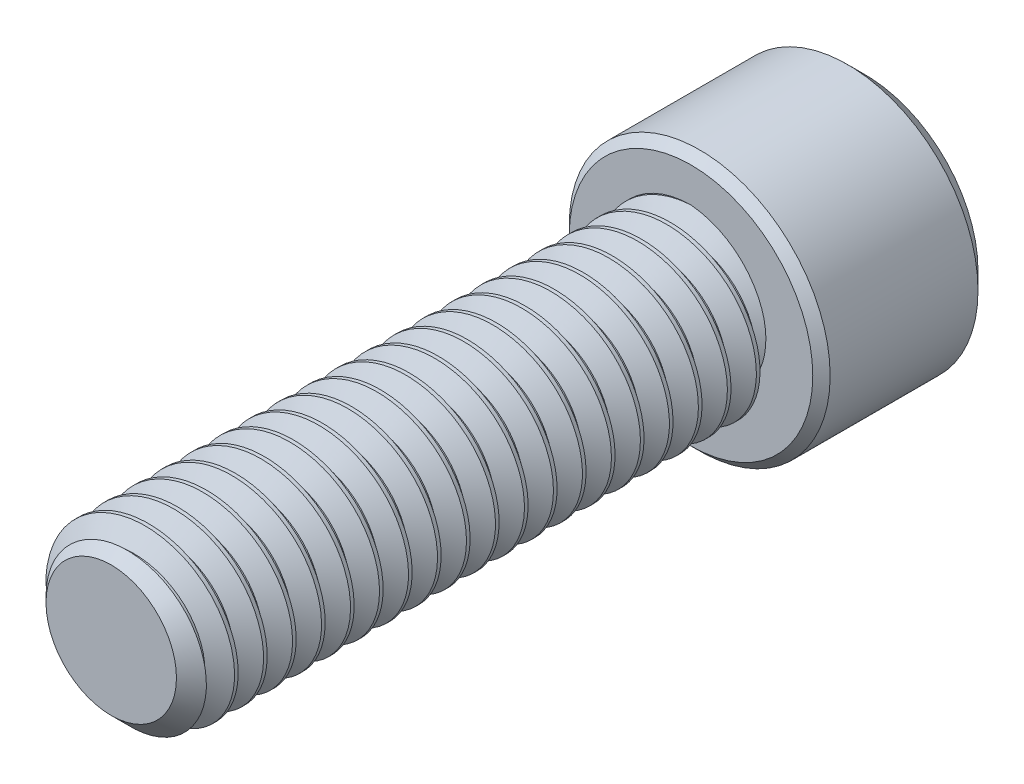
SolidWorks part; units mm, degrees
ref_plane "Front Plane" through (0, 0, 0) normal (0, 0, 1) x (1, 0, 0)
ref_plane "Top Plane" through (0, 0, 0) normal (0, 1, 0) x (1, 0, 0)
ref_plane "Right Plane" through (0, 0, 0) normal (1, 0, 0) x (0, 0, -1)
sketch "Sketch1" plane through (0, 0, 0) normal (0, 0, 1) x (1, 0, 0)
  line L0 (0, 4.7625) -> (0, -4.7625) construction
  circle A0 centre (0, 0) radius 4.7625
  dimension "OD" = 9.525
extrude "Extrude1" add sketch "Sketch1" against normal blind 31.75
sketch "Sketch2" plane through (0, 0, 0) normal (0, 0, 1) x (1, 0, 0)
  circle A0 centre (0, 0) radius 4.7625 construction
  circle A1 centre (0, 0) radius 4.7625
curve "Helix/Spiral1" pitch 1.5875 height 33.3375 turns 21 parameters "pitch"=1.5875
chamfer "Chamfer3" distance 1.1906 angle 45 1 edges at (4.7625, 0, 0)
sketch "Sketch3" plane through (0, 0, 0) normal (1, 0, 0) x (0, 0, -1)
  line L0 (-1.3891, 4.7625) -> (-0.7938, 3.7314)
  line L1 (-0.7938, 3.7314) -> (-0.5953, 3.7314)
  line L2 (-0.5953, 3.7314) -> (0, 4.7625)
  line L3 (-1.3891, 4.7625) -> (0, 4.7625)
  line L4 (-0.6945, 4.7625) -> (-0.6945, 3.7314) construction
  line L5 (-1.0914, 4.2469) -> (-0.2977, 4.2469) construction
  line L6 (0, 4.7625) -> (0, -4.7625) construction
  dimension "D1" = 0.1984
  dimension "D2" = 0.7937
  dimension "D3" = 60
sweep "Cut-Sweep1" cut profiles "Sketch3" path "Helix/Spiral1"
sketch "Sketch6" plane through (0, 0, -31.75) normal (0, 0, -1) x (-1, 0, 0)
  circle A0 centre (0, 0) radius 7.1438
  dimension "head dia" = 14.2875
extrude "Extrude2" add sketch "Sketch6" along normal blind 9.525
sketch "Sketch7" plane through (0, 0, -41.275) normal (0, 0, -1) x (-1, 0, 0)
  line L1 (0, 4.5827) -> (-3.9688, 2.2914)
  line L2 (-3.9688, 2.2914) -> (-3.9688, -2.2914)
  line L3 (-3.9688, -2.2914) -> (0, -4.5827)
  line L4 (0, -4.5827) -> (3.9688, -2.2914)
  line L5 (3.9688, -2.2914) -> (3.9687, 2.2914)
  line L6 (3.9687, 2.2914) -> (0, 4.5827)
  circle A0 centre (0, 0) radius 3.9688 construction
  dimension "hex dia" = 7.9375
extrude "Cut-Extrude1" cut sketch "Sketch7" against normal blind 5.9531
sketch "Sketch8" plane through (0, 0, -41.275) normal (0, 0, -1) x (-1, 0, 0)
  circle A0 centre (0, 0) radius 4.5827
extrude "Cut-Extrude2" cut sketch "Sketch8" against normal blind 0.9525 draft 45
chamfer "Chamfer1" distance 0.9525 angle 45 1 edges at (-7.1438, 0, -41.275)
chamfer "Chamfer2" distance 0.4763 angle 45 1 edges at (-7.1438, 0, -31.75)
sketch "Sketch9" plane through (0, 0, 0) normal (1, 0, 0) x (0, 0, -1)
  line L0 (0, 4.7625) -> (0, -4.7625) construction
  line L1 (8.7313, 4.7625) -> (8.7313, -4.7625) construction
  line L2 (31.75, 7.1437) -> (31.75, -7.1438) construction
  line L3 (41.275, 7.1437) -> (41.275, -7.1437) construction
  line L4 (41.275, 0) -> (0, 0) construction
  dimension "D1" = 8.7312
  dimension "D2" = 9.525
  dimension "D3" = 14.2875
  dimension "D4" = 0.635
  dimension "D5" = 0.3302
equation "\"D3@Helix/Spiral1\" = \"screw length@Extrude1\"+\"pitch@Helix/Spiral1\""
equation "\"D1@Sketch3\" = \"pitch@Helix/Spiral1\"*.125"
equation "\"D2@Sketch3\" = \"pitch@Helix/Spiral1\"*.5"
equation "\"D1@Cut-Extrude1\" = \"hex dia@Sketch7\"*.75"
equation "\"D1@Chamfer1\" = \"head depth@Extrude2\"/10"
equation "\"D1@Sketch9\" = \"pitch@Helix/Spiral1\"*5.5"
equation "\"D1@Chamfer2\" = \"D1@Chamfer1\"/2"
equation "\"D1@Cut-Extrude2\" = \"D1@Chamfer2\"*2"
equation "\"D1@Chamfer3\" = \"pitch@Helix/Spiral1\"*.750"
equation "\"D2@Sketch9\" = \"head depth@Extrude2\""
equation "\"D3@Sketch9\" = \"head dia@Sketch6\""
equation "\"D4@Sketch9\" = \"screw length@Extrude1\""
